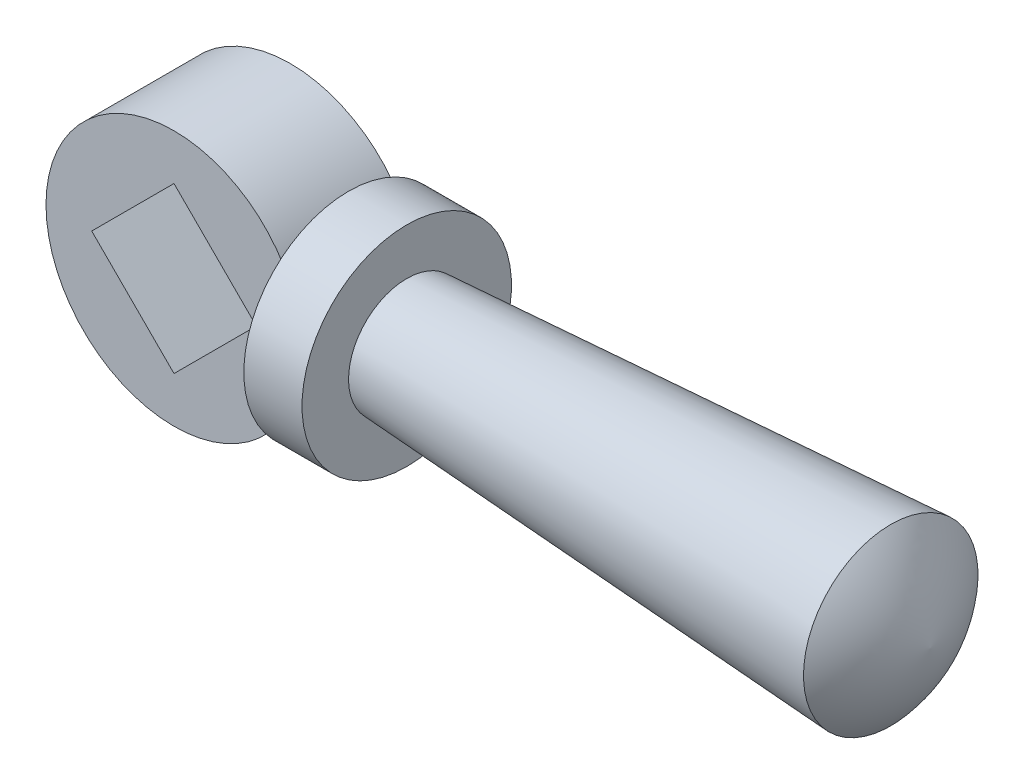
SolidWorks part; units mm, degrees
ref_plane "Спереди" through (0, 0, 0) normal (0, 0, 1) x (1, 0, 0)
ref_plane "Сверху" through (0, 0, 0) normal (0, 1, 0) x (1, 0, 0)
ref_plane "Справа" through (0, 0, 0) normal (1, 0, 0) x (0, 0, -1)
sketch "Эскиз1" plane through (0, 0, 0) normal (0, 0, 1) x (1, 0, 0)
  line L0 (0, -1.8176) -> (46.5927, -1.8176)
  line L2 (46.5927, -9.3176) -> (5, -6.8176)
  line L3 (5, -6.8176) -> (5, -10.8176)
  line L4 (0, -1.8176) -> (0, -10.8176)
  line L5 (0, -10.8176) -> (5, -10.8176)
  line L6 (46.5927, -1.8176) -> (50, -1.8176)
  line L7 (0, -1.8176) -> (-10, -1.8176) construction
  arc A0 (50, -1.8176) -> (46.5927, -9.3176) centre (35.1646, 0.3983) cw
  point P9 (0, 0)
  dimension "D3" = 15
  dimension "D1" = 5
  dimension "D2" = 9
  dimension "D4" = 7.5
  dimension "D5" = 5
  dimension "D6" = 10
  dimension "D7" = 60
revolve "Повернуть1" add sketch "Эскиз1" angle 360 about L7
sketch "Эскиз2" plane through (0, 0, 0) normal (0, 0, 1) x (1, 0, 0)
  line L0 (-10, -1.8176) -> (-10, 5.2535) construction
  line L1 (-10, 5.2535) -> (-2.9289, -1.8176)
  line L2 (0, -1.8176) -> (-10, -1.8176) construction
  line L3 (-10, -1.8176) -> (-14.2231, 2.4056) construction
  line L4 (-17.0711, -1.8176) -> (-10, -8.8886)
  line L5 (-2.9289, -1.8176) -> (-10, -8.8886)
  line L6 (-10, 5.2535) -> (-17.0711, -1.8176)
  circle A0 centre (-10, -1.8176) radius 11
  dimension "D1" = 22
  dimension "D2" = 45
  dimension "D3" = 10
extrude "Бобышка-Вытянуть1" add sketch "Эскиз2" along normal blind 5 and the other way blind 5
